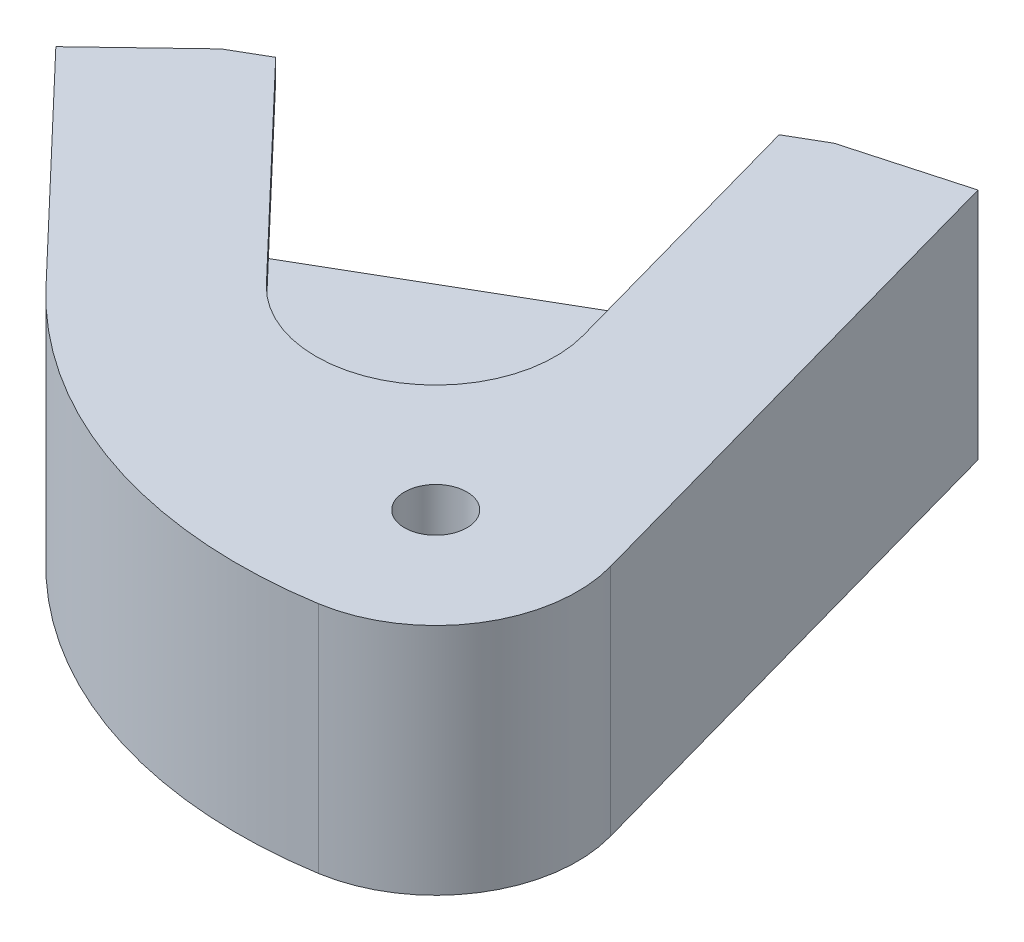
SolidWorks part; units mm, degrees
material "1060 Alloy"
ref_plane "Front Plane" through (0, 0, 0) normal (0, 0, 1) x (1, 0, 0)
ref_plane "Top Plane" through (0, 0, 0) normal (0, 1, 0) x (1, 0, 0)
ref_plane "Right Plane" through (0, 0, 0) normal (1, 0, 0) x (0, 0, -1)
sketch "Sketch1" plane through (0, 0, 0) normal (0, 1, 0) x (1, 0, 0)
  line L0 (-54.4954, 86.3958) -> (0, 60) construction
  line L1 (0, 60) -> (54.4954, 86.3958) construction
  line L2 (65.3716, 76.1292) -> (40, 15) construction
  line L3 (40, 15) -> (65.6883, -77.0455) construction
  line L4 (52.194, -84.7177) -> (0, -30) construction
  line L5 (0, -30) -> (-52.194, -84.7177) construction
  line L6 (-65.6883, -77.0455) -> (-40, 15) construction
  line L7 (-40, 15) -> (-65.3716, 76.1292) construction
  line L8 (-68.5894, 68.5894) -> (68.5894, -68.5894) construction
  line L9 (-42, 75) -> (-36, 75) construction
  line L10 (-42, 75) -> (-42, 55) construction
  line L11 (-42, 55) -> (-36, 55) construction
  line L12 (-36, 75) -> (-36, 55) construction
  line L13 (-42, 75) -> (-36, 55) construction
  line L14 (-42, 55) -> (-36, 75) construction
  line L15 (36, 75) -> (42, 75) construction
  line L16 (36, 75) -> (36, 55) construction
  line L17 (36, 55) -> (42, 55) construction
  line L18 (42, 75) -> (42, 55) construction
  line L19 (36, 75) -> (42, 55) construction
  line L20 (36, 55) -> (42, 75) construction
  line L21 (36, -45) -> (42, -45) construction
  line L22 (36, -45) -> (36, -65) construction
  line L23 (36, -65) -> (42, -65) construction
  line L24 (42, -45) -> (42, -65) construction
  line L25 (36, -45) -> (42, -65) construction
  line L26 (36, -65) -> (42, -45) construction
  line L27 (-42, -45) -> (-36, -45) construction
  line L28 (-42, -45) -> (-42, -65) construction
  line L29 (-42, -65) -> (-36, -65) construction
  line L30 (-36, -45) -> (-36, -65) construction
  line L31 (-42, -45) -> (-36, -65) construction
  line L32 (-42, -65) -> (-36, -45) construction
  line L33 (97, 40.1787) -> (40.1787, 97) construction
  line L34 (40.1787, 97) -> (-40.1787, 97) construction
  line L35 (-40.1787, 97) -> (-97, 40.1787) construction
  line L36 (-97, 40.1787) -> (-97, -40.1787) construction
  line L37 (-97, -40.1787) -> (-40.1787, -97) construction
  line L38 (-40.1787, -97) -> (40.1787, -97) construction
  line L39 (40.1787, -97) -> (97, -40.1787) construction
  line L40 (97, -40.1787) -> (97, 40.1787) construction
  line L41 (68.5894, 68.5894) -> (-68.5894, -68.5894) construction
  line L42 (41.8649, -74.1065) -> (52.2182, -84.9605)
  line L43 (111, -45.9777) -> (111, 45.9777) construction
  line L44 (111, 45.9777) -> (45.9777, 111) construction
  line L45 (45.9777, 111) -> (-45.9777, 111) construction
  line L46 (-45.9777, 111) -> (-111, 45.9777) construction
  line L47 (-111, 45.9777) -> (-111, -45.9777) construction
  line L48 (-111, -45.9777) -> (-45.9777, -111) construction
  line L49 (-45.9777, -111) -> (45.9777, -111) construction
  line L50 (45.9777, -111) -> (111, -45.9777) construction
  line L51 (65.835, -77.0045) -> (61.8028, -62.5566)
  line L52 (61.8028, -62.5566) -> (67.582, -60.9438)
  line L53 (67.582, -60.9438) -> (74.8926, -87.139)
  line L54 (47.9744, -89.2043) -> (37.5233, -78.2479)
  line L55 (37.5233, -78.2479) -> (41.8649, -74.1065)
  circle A0 centre (-57.9828, 79.196) radius 1.5 construction
  circle A1 centre (57.9828, 79.196) radius 1.5 construction
  circle A2 centre (-57.9828, -79.196) radius 1.5 construction
  circle A3 centre (57.9828, -79.196) radius 1.5 construction
  arc A4 (-54.4954, 86.3958) -> (-65.3716, 76.1292) centre (-57.9828, 79.196) ccw construction
  arc A5 (54.4954, 86.3958) -> (65.3716, 76.1292) centre (57.9828, 79.196) cw construction
  arc A6 (-65.6883, -77.0455) -> (-52.194, -84.7177) centre (-57.9828, -79.196) ccw construction
  arc A7 (65.6883, -77.0455) -> (52.194, -84.7177) centre (57.9828, -79.196) cw construction
  circle A8 centre (0, 0) radius 97 construction
  circle A9 centre (-39, 65) radius 1.5 construction
  circle A10 centre (39, 65) radius 1.5 construction
  circle A11 centre (39, -55) radius 1.5 construction
  circle A12 centre (-39, -55) radius 1.5 construction
  circle A13 centre (0, 0) radius 111 construction
  circle A14 centre (67.8823, -89.0955) radius 1.6
  arc A15 (52.2182, -84.9605) -> (65.835, -77.0045) centre (57.9828, -79.196) ccw
  arc A16 (74.8926, -87.139) -> (69.051, -96.2792) centre (67.8823, -89.0955) cw
  arc A17 (69.051, -96.2792) -> (47.9744, -89.2043) centre (65.2231, -72.7512) cw
  ellipse E0 centre (0, 15) end of major axis (0, 60) minor radius 40 construction
  dimension "D5" = 3
  dimension "D6" = 45
  dimension "D7" = 8
  dimension "D12" = 3
  dimension "D20" = 3.2
  dimension "D2" = 111
  dimension "D3" = 15
  dimension "D4" = 15
  dimension "D8" = 120
  dimension "D9" = 78
  dimension "D10" = 15
  dimension "D11" = 55
  dimension "D13" = 40
  dimension "D14" = 39
  dimension "D15" = 20
  dimension "D16" = 6
  dimension "D17" = 97
  dimension "D18" = 15
  dimension "D19" = 15
  dimension "D21" = 0.3
  dimension "D22" = 6
  dimension "D23" = 6
  dimension "D24" = 15
extrude "Boss-Extrude1" add sketch "Sketch1" along normal blind 6
sketch "Sketch7" plane through (0, 0, 0) normal (0, -1, 0) x (1, 0, 0)
  line L0 (37.5233, 78.2479) -> (41.8649, 74.1065)
  line L1 (41.8649, 74.1065) -> (61.8028, 62.5566)
  line L2 (61.8028, 62.5566) -> (67.582, 60.9438)
  line L3 (67.582, 60.9438) -> (74.8926, 87.139)
  line L4 (47.9744, 89.2043) -> (37.5233, 78.2479)
  arc A0 (74.8926, 87.139) -> (69.051, 96.2792) centre (67.8823, 89.0955) ccw
  arc A1 (69.051, 96.2792) -> (47.9744, 89.2043) centre (65.2231, 72.7512) ccw
  circle A2 centre (67.8823, 89.0955) radius 1.6
  circle A3 centre (57.9828, 79.196) radius 1.6
  dimension "D1" = 3.2
extrude "Boss-Extrude3" add sketch "Sketch7" along normal blind 3
sketch "Sketch8" plane through (0, 6, 0) normal (0, 1, 0) x (1, 0, 0)
  line L0 (41.8649, -74.1065) -> (37.5233, -78.2479)
  line L1 (37.5233, -78.2479) -> (47.9744, -89.2043)
  line L2 (74.8926, -87.139) -> (67.582, -60.9438)
  line L3 (67.582, -60.9438) -> (61.8028, -62.5566)
  line L4 (61.8028, -62.5566) -> (60.0154, -63.5921)
  line L5 (41.8649, -74.1065) -> (61.8028, -62.5566) construction
  line L6 (60.0154, -63.5921) -> (63.9086, -77.5422)
  line L7 (53.531, -83.4424) -> (43.6431, -73.0764)
  line L8 (43.6431, -73.0764) -> (41.8649, -74.1065)
  line L9 (52.2182, -84.9605) -> (41.8649, -74.1065) construction
  line L10 (61.8028, -62.5566) -> (65.835, -77.0045) construction
  arc A0 (47.9744, -89.2043) -> (69.051, -96.2792) centre (65.2231, -72.7512) ccw
  arc A1 (69.051, -96.2792) -> (74.8926, -87.139) centre (67.8823, -89.0955) ccw
  arc A2 (63.9086, -77.5422) -> (53.531, -83.4424) centre (57.9828, -79.196) cw
  arc A3 (52.2182, -84.9605) -> (65.835, -77.0045) centre (57.9828, -79.196) ccw construction
  circle A4 centre (67.8823, -89.0955) radius 1.6
  dimension "D1" = 2
extrude "Boss-Extrude4" add sketch "Sketch8" along normal blind 3
chamfer "Chamfer1" distance 2 angle 45 3 edges at (48.5871, 6, 78.2594) (61.0235, 6, 84.5442) (61.962, 6, 70.5671)
equation "\"D14@Sketch1\"=\"D9@Sketch1\"/2"
